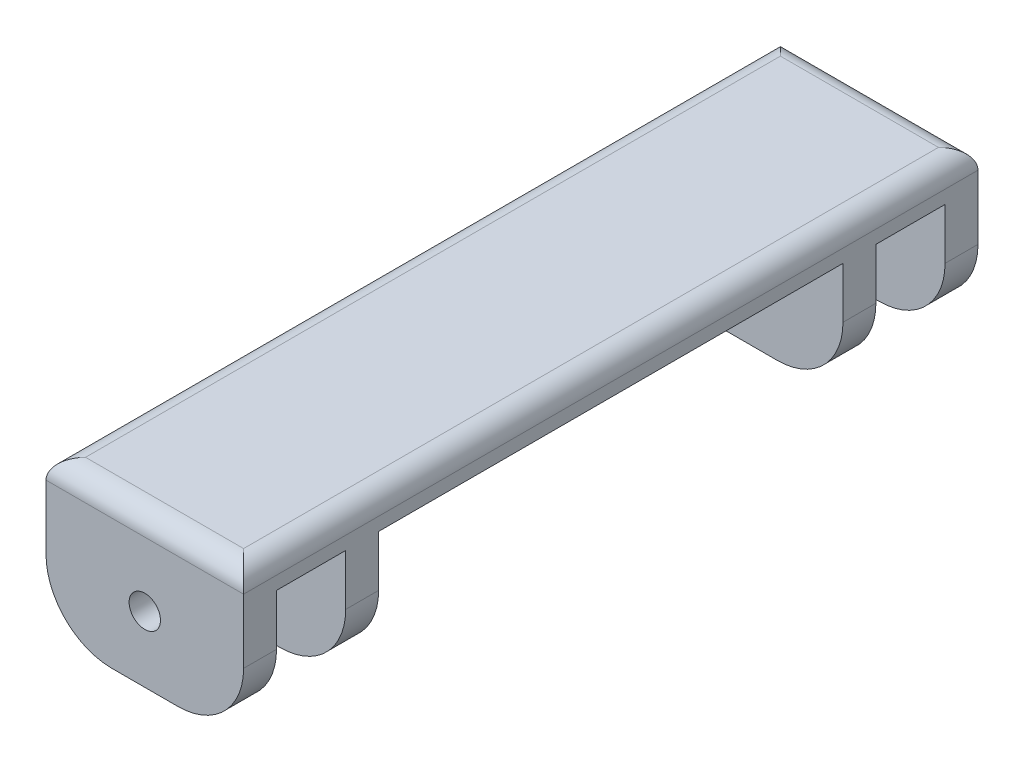
SolidWorks part; units mm, degrees
ref_plane "Plan de face" through (0, 0, 0) normal (0, 0, 1) x (1, 0, 0)
ref_plane "Plan de dessus" through (0, 0, 0) normal (0, 1, 0) x (1, 0, 0)
ref_plane "Plan de droite" through (0, 0, 0) normal (1, 0, 0) x (0, 0, -1)
sketch "Esquisse1" plane through (0, 0, 0) normal (0, 0, 1) x (1, 0, 0)
  line L1 (0, 0) -> (30, 0)
  line L2 (0, 0) -> (0, 5)
  line L3 (0, 5) -> (30, 5)
  line L4 (30, 0) -> (30, 5)
  dimension "D1" = 30
  dimension "7" = 5
extrude "Boss.-Extru.1" add sketch "Esquisse1" along normal blind 111.5
sketch "Esquisse2" plane through (0, 0, 0) normal (0, -1, 0) x (1, 0, 0)
  line L0 (30, 111.5) -> (30, 0) construction
  line L1 (0, 0) -> (30, 0)
  line L2 (0, 0) -> (0, 5)
  line L3 (0, 5) -> (30, 5)
  line L4 (30, 0) -> (30, 5)
  line L5 (0, 111.5) -> (0, 0) construction
  line L6 (30, 15.5) -> (0, 15.5)
  line L7 (30, 15.5) -> (30, 20.5)
  line L8 (30, 20.5) -> (0, 20.5)
  line L9 (0, 15.5) -> (0, 20.5)
  line L11 (0, 111.5) -> (30, 111.5)
  line L12 (0, 111.5) -> (0, 106.5)
  line L13 (0, 106.5) -> (30, 106.5)
  line L14 (30, 111.5) -> (30, 106.5)
  line L15 (30, 96) -> (0, 96)
  line L16 (30, 96) -> (30, 91)
  line L17 (30, 91) -> (0, 91)
  line L18 (0, 96) -> (0, 91)
  dimension "D1" = 5
  dimension "D2" = 5
  dimension "D3" = 5
  dimension "D4" = 5
  dimension "D5" = 10.5
  dimension "D6" = 10.5
extrude "Boss.-Extru.2" add sketch "Esquisse2" along normal blind 17.75
hole_wizard "Perçage pour écrous auto-bloquants 300® #6 (SP)1" positions "Esquisse3" profile "Esquisse4" hole size "#6-32" standard "PEM® Inch" end condition through all
sketch "Esquisse3" plane through (0, 0, 111.5) normal (0, 0, 1) x (1, 0, 0)
  line L0 (0, -7.75) -> (15, -7.75) construction
  line L1 (0, 5) -> (0, -17.75) construction
  line L2 (15, -7.75) -> (30, -7.75) construction
  line L3 (30, -17.75) -> (30, 5) construction
  line L5 (30, -17.75) -> (0, -17.75) construction
  point P0 (15, -7.75)
  dimension "D1" = 10
sketch "Esquisse4" plane through (15, -7.75, 111.5) normal (1, 0, 0) x (0, -1, 0)
  line L0 (0, 0) -> (0, 111.5)
  line L1 (0, 111.5) -> (2.3812, 111.5)
  line L2 (2.3812, 111.5) -> (2.3812, 0)
  line L5 (2.3812, 0) -> (0, 0)
  line L11 (0, -6.35) -> (0, 107.95) construction
  dimension "Diamètre du perçage jusqu'au prochain" = 4.7625
  dimension "Profondeur du perçage jusqu'au prochain" = 111.5
fillet "Congé1" radius 10 8 edges at (0, -17.75, 2.5) (30, -17.75, 2.5) (30, -17.75, 93.5) (30, -17.75, 109) (0, -17.75, 93.5) (0, -17.75, 109) (0, -17.75, 18) (30, -17.75, 18)
fillet "Congé2" radius 3 4 edges at (30, 5, 55.75) (15, 5, 111.5) (0, 5, 55.75) (15, 5, 0)
